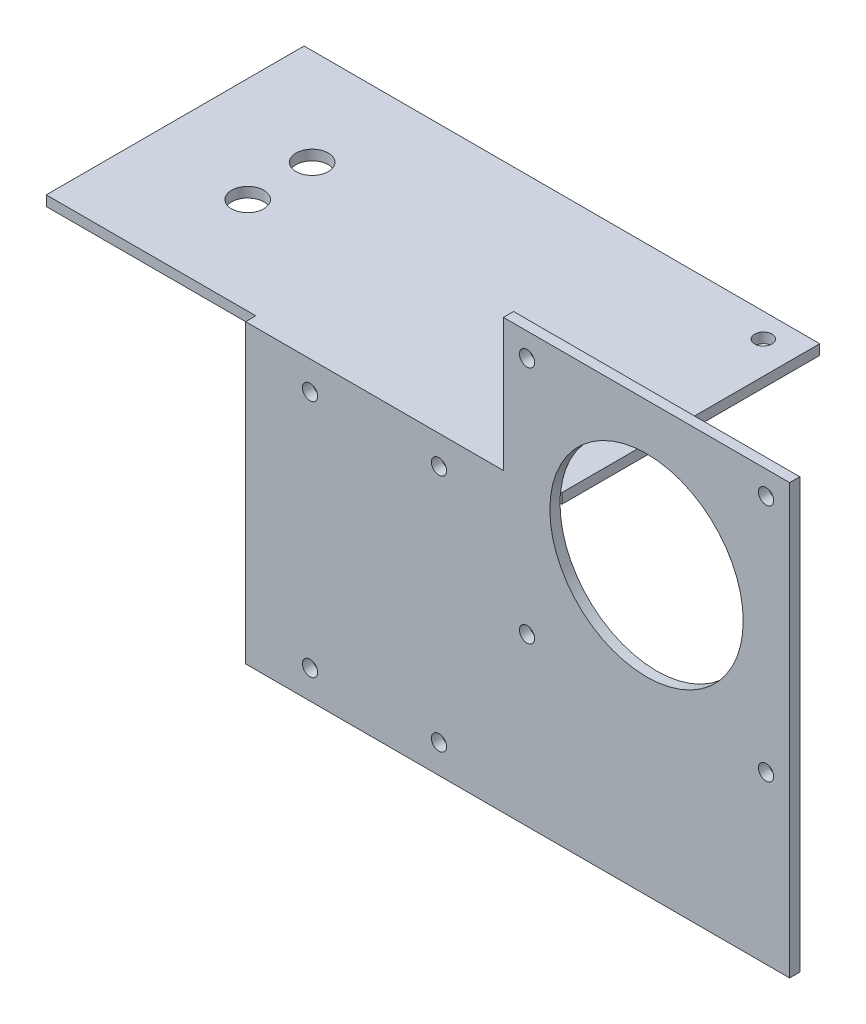
SolidWorks part; units mm, degrees
ref_plane "Front Plane" through (0, 0, 0) normal (0, 0, 1) x (1, 0, 0)
ref_plane "Top Plane" through (0, 0, 0) normal (0, 1, 0) x (1, 0, 0)
ref_plane "Right Plane" through (0, 0, 0) normal (1, 0, 0) x (0, 0, -1)
sketch "Sketch1" plane through (0, 0, 0) normal (0, 0, 1) x (1, 0, 0)
  line L0 (55.45, 32.782) -> (102.55, 32.782) construction
  line L1 (0, 58.4) -> (50.8, 58.4)
  line L2 (0, 58.4) -> (0, 0)
  line L3 (0, 0) -> (107.2, 0)
  line L4 (107.2, 84.532) -> (107.2, 0)
  line L5 (102.55, 79.882) -> (102.55, 32.782) construction
  line L6 (12.7, 52.75) -> (12.7, 5.65) construction
  line L7 (55.45, 32.782) -> (55.45, 79.882) construction
  line L8 (55.45, 79.882) -> (102.55, 79.882) construction
  line L9 (38.1, 52.75) -> (38.1, 5.65) construction
  line L10 (55.45, 79.882) -> (102.55, 32.782) construction
  line L11 (102.55, 79.882) -> (55.45, 32.782) construction
  line L12 (12.7, 52.75) -> (38.1, 52.75) construction
  line L13 (12.7, 5.65) -> (38.1, 5.65) construction
  line L15 (107.2, 84.532) -> (50.8, 84.532)
  line L16 (50.8, 84.532) -> (50.8, 58.4)
  circle A0 centre (102.55, 79.882) radius 1.5
  circle A1 centre (102.55, 32.782) radius 1.5
  circle A2 centre (55.45, 32.782) radius 1.5
  circle A3 centre (55.45, 79.882) radius 1.5
  circle A4 centre (12.7, 52.75) radius 1.5
  circle A5 centre (38.1, 52.75) radius 1.5
  circle A6 centre (12.7, 5.65) radius 1.5
  circle A7 centre (38.1, 5.65) radius 1.5
  circle A8 centre (79, 56.332) radius 19.05
  point P21 (12.7, 29.2)
  point P22 (0, 29.2)
  dimension "D3" = 3
  dimension "D10" = 38.1
  dimension "D1" = 58.4
  dimension "D2" = 107.2
  dimension "D4" = 47.1
  dimension "D5" = 47.1
  dimension "D6" = 2.068
  dimension "D7" = 25.4
  dimension "D8" = 4.65
  dimension "D9" = 12.7
  dimension "D11" = 47.1
  dimension "D12" = 4.65
  dimension "D13" = 4.65
extrude "Boss-Extrude1" add sketch "Sketch1" against normal blind 2
sketch "Sketch2" plane through (0, 0, -2) normal (0, 0, -1) x (-1, 0, 0)
  line L0 (0, 56.4) -> (41.275, 56.4)
  line L1 (0, 58.4) -> (0, 0) construction
  line L2 (0, 56.4) -> (-60.325, 56.4)
  line L3 (-60.325, 56.4) -> (-60.325, 58.4)
  line L4 (-50.8, 58.4) -> (0, 58.4) construction
  line L5 (-60.325, 58.4) -> (0, 58.4)
  line L6 (41.275, 56.4) -> (41.275, 58.4)
  line L7 (41.275, 58.4) -> (0, 58.4)
  dimension "D1" = 60.325
  dimension "D2" = 41.275
  dimension "D3" = 2
extrude "Boss-Extrude2" add sketch "Sketch2" along normal blind 50.8
sketch "Sketch3" plane through (0, 58.4, 0) normal (0, 1, 0) x (1, 0, 0)
  line L0 (53.975, 48.0375) -> (53.975, 6.7625) construction
  line L1 (-41.275, 52.8) -> (60.325, 52.8) construction
  line L2 (60.325, 52.8) -> (60.325, 2) construction
  line L3 (-20.6375, 33.75) -> (-20.6375, 21.05) construction
  line L4 (-41.275, 52.8) -> (60.325, 52.8) construction
  line L5 (-41.275, 52.8) -> (-41.275, 2) construction
  circle A0 centre (53.975, 48.0375) radius 1.7
  circle A1 centre (53.975, 6.7625) radius 1.7
  circle A2 centre (-20.6375, 33.75) radius 3.175
  circle A3 centre (-20.6375, 21.05) radius 3.175
  dimension "D1" = 3.4
  dimension "D2" = 41.275
  dimension "D5" = 6.35
  dimension "D6" = 6.35
  dimension "D3" = 4.7625
  dimension "D4" = 6.35
  dimension "D7" = 12.7
  dimension "D8" = 19.05
  dimension "D9" = 20.6375
extrude "Cut-Extrude1" cut sketch "Sketch3" against normal through all
